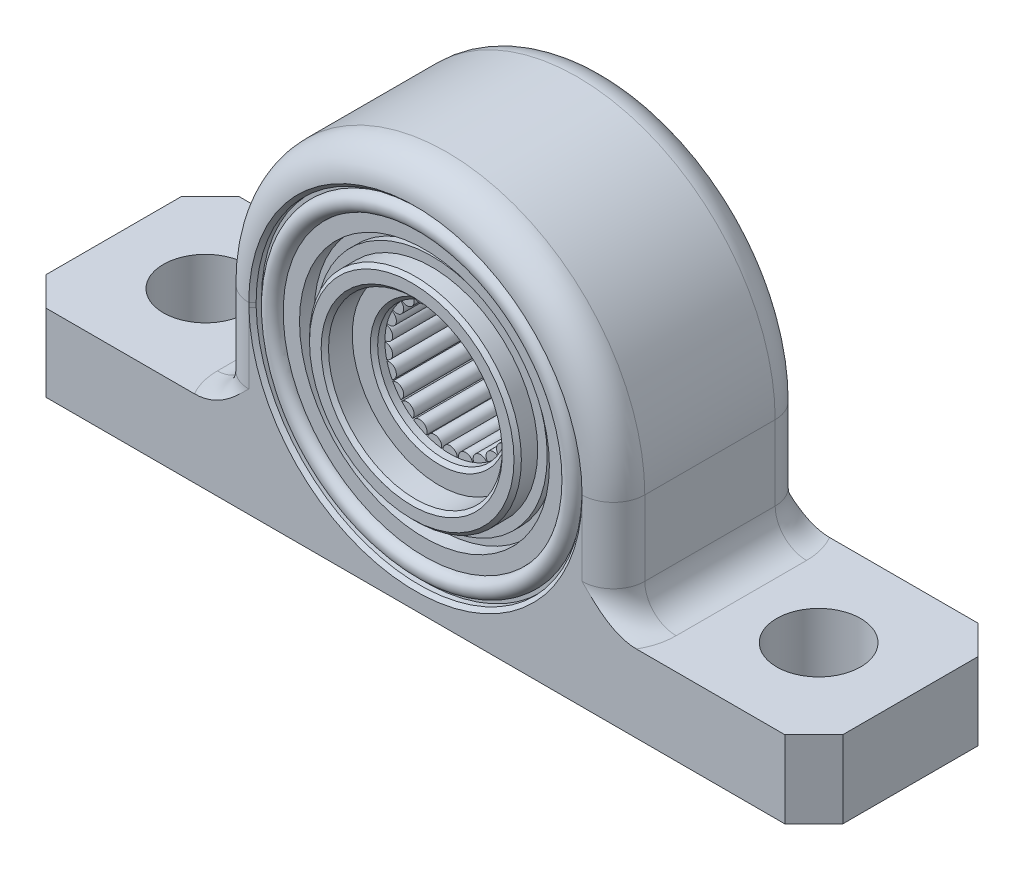
SolidWorks part; units mm, degrees
ref_plane "Front Plane" through (0, 0, 0) normal (0, 0, 1) x (1, 0, 0)
ref_plane "Top Plane" through (0, 0, 0) normal (0, 1, 0) x (1, 0, 0)
ref_plane "Right Plane" through (0, 0, 0) normal (1, 0, 0) x (0, 0, -1)
sketch "Sketch1" plane through (0, 0, 0) normal (0, 0, 1) x (1, 0, 0)
  line L0 (0, 19.75) -> (0, -19.75) construction
  line L1 (-41.25, -19.75) -> (41.25, -19.75) construction
  line L2 (-31.75, -19.75) -> (31.75, -19.75) construction
  line L3 (-41.25, -19.75) -> (-41.25, -11.75)
  line L4 (-41.25, -11.75) -> (-20.5, -11.75)
  line L5 (-20.5, -0.75) -> (-20.5, -11.75)
  line L6 (-23.75, -19.75) -> (-23.75, -11.75) construction
  circle A0 centre (-31.75, -19.75) radius 4.35
  circle A1 centre (31.75, -19.75) radius 4.35
  circle A2 centre (0, -0.75) radius 6
  circle A3 centre (0, -0.75) radius 20.5
  circle A4 centre (-31.75, -19.75) radius 8
  circle A5 centre (0, -0.75) radius 16.875
  circle A6 centre (0, -0.75) radius 9
  circle A7 centre (0, -0.75) radius 6.75 construction
  point P5 (0, -11.75)
  point P6 (0, -0.75)
  point P7 (-31.75, -19.75)
  point P8 (31.75, -19.75)
  point P22 (0, 5.25)
  point P23 (0, 16.125)
  point P25 (0, 13.875)
  point P26 (0, 12.1875)
  point P27 (0, 10.2187)
  point P28 (0, 8.25)
  dimension "D1" = 3.25
  dimension "Mounting Hole" = 8.7
  dimension "ID" = 12
  dimension "D3" = 10.875
  dimension "D4" = 18
  dimension "D9" = 13.5
  dimension "Height" = 39.5
  dimension "Length" = 82.5
  dimension "Lit G" = 8
  dimension "Center Height" = 19
  dimension "Mounting Center" = 63.5
  dimension "D2" = 14.5
  dimension "D5" = 7.875
  dimension "D6" = 2.25
  dimension "D7" = 1.9687
  dimension "D8" = 1.9687
sketch "Sketch3" plane through (0, 0, 0) normal (0, 1, 0) x (1, 0, 0)
  line L0 (0, 10) -> (0, -10) construction
  point P2 (0, -10)
  point P4 (0, 9.5)
  dimension "Width" = 20
  dimension "CAD C" = 20
  dimension "D" = 19.5
sketch "Sketch6" plane through (0, 0, 0) normal (1, 0, 0) x (0, 0, -1)
  line L0 (-9.0655, 15.744) -> (-9.0655, 16.125)
  line L1 (-10, 16.125) -> (10, 16.125) construction
  line L2 (-10, 16.125) -> (-10, -0.75) construction
  line L3 (-10, -0.75) -> (10, -0.75) construction
  line L4 (10, 16.125) -> (10, -0.75) construction
  line L5 (-9.0655, 13.875) -> (-9.0655, 12.1875)
  line L6 (-7.5415, 12.1875) -> (-9.0655, 12.1875)
  line L7 (-8.3035, 11.2031) -> (-8.3035, 10.2187)
  line L8 (-8.3035, 10.2187) -> (-10.381, 10.2187)
  line L9 (-10.381, 10.2187) -> (-10.381, 8.25)
  line L10 (-8.3035, 11.2031) -> (-7.5415, 11.2031)
  line L11 (-7.5415, 11.2031) -> (-7.5415, 12.1875)
  line L12 (-10.381, 8.25) -> (-7.5415, 8.25)
  line L13 (-7.5415, 8.25) -> (-7.5415, 5.25)
  line L14 (-7.5415, 5.25) -> (7.5415, 5.25)
  line L15 (-9.0655, 16.125) -> (9.0655, 16.125)
  line L16 (0, -0.75) -> (0, 32.5437) construction
  line L17 (0, 19.75) -> (0, -19.75) construction
  line L18 (0, 19.75) -> (0, -21.25) construction
  line L19 (7.5415, 8.25) -> (7.5415, 5.25)
  line L20 (10.381, 8.25) -> (7.5415, 8.25)
  line L21 (7.5415, 11.2031) -> (7.5415, 12.1875)
  line L22 (8.3035, 11.2031) -> (7.5415, 11.2031)
  line L23 (10.381, 10.2187) -> (10.381, 8.25)
  line L24 (8.3035, 10.2187) -> (10.381, 10.2187)
  line L25 (8.3035, 11.2031) -> (8.3035, 10.2187)
  line L26 (7.5415, 12.1875) -> (9.0655, 12.1875)
  line L27 (9.0655, 13.875) -> (9.0655, 12.1875)
  line L28 (9.0655, 15.744) -> (9.0655, 16.125)
  arc A0 (-9.0655, 15.744) -> (-9.0655, 13.875) centre (-9.0655, 14.8095) ccw
  arc A1 (9.0655, 15.744) -> (9.0655, 13.875) centre (9.0655, 14.8095) cw
  point P40 (0, 16.125)
  point P41 (0, 5.25)
  dimension "D1" = 0.381
  dimension "D2" = 0.381
  dimension "D3" = 1.524
  dimension "D4" = 0.762
  dimension "D5" = 0.762
  dimension "D6" = 15.083
revolve "Revolve1" add sketch "Sketch6" angle 360 about L3
sketch "Sketch7" plane through (0, 0, 0) normal (0, 0, 1) x (1, 0, 0)
  line L0 (0, 19.75) -> (0, -19.75) construction
  line L1 (-0.75, 6) -> (0, -0.75) construction
  line L2 (0, -0.75) -> (0.75, 6) construction
  circle A0 centre (0, 6) radius 0.75
  circle A1 centre (0, -0.75) radius 6.75 construction
  circle A2 centre (0, -0.75) radius 6 construction
  dimension "D1" = 1.5
  dimension "D2" = 12.68
sketch "Sketch8" plane through (0, 0, 7.5415) normal (0, 0, 1) x (1, 0, 0)
  circle A0 centre (0, -0.75) radius 6.75 construction
  circle A1 centre (0, -0.75) radius 6.75
extrude "Cut-Extrude2" cut sketch "Sketch8" against normal through all
sketch "Sketch9" plane through (0, 0, 0) normal (0, 0, 1) x (1, 0, 0)
  circle A0 centre (0, 6) radius 0.75 construction
  circle A1 centre (0, 6) radius 0.75
extrude "Boss-Extrude2" add sketch "Sketch9" along normal mid plane 12.8205
pattern_circular "CirPattern1" count 26 over 360 of "Boss-Extrude2"
chamfer "Chamfer2" distance 0.381 angle 45 6 edges at (9, -0.75, -10.381) (10.9688, -0.75, -10.381) (10.9688, -0.75, 10.381) (9, -0.75, 10.381) (6.75, -0.75, -7.5415) (6.75, -0.75, 7.5415)
sketch "Sketch4" plane through (0, 0, 0) normal (0, 0, 1) x (1, 0, 0)
  line L0 (-41.25, -19.75) -> (-41.25, -11.75) construction
  line L1 (-41.25, -11.75) -> (-20.5, -11.75) construction
  line L2 (-41.25, -19.75) -> (41.25, -19.75) construction
  line L3 (-41.25, -19.75) -> (-41.25, -11.75)
  line L4 (-41.25, -11.75) -> (-20.5, -11.75)
  line L5 (-41.25, -19.75) -> (41.25, -19.75)
  line L6 (-20.5, -0.75) -> (-20.5, -11.75) construction
  line L7 (-20.5, -0.75) -> (-20.5, -11.75)
  line L8 (0, 19.75) -> (0, -19.75) construction
  line L9 (20.5, -0.75) -> (20.5, -11.75)
  line L10 (41.25, -11.75) -> (20.5, -11.75)
  line L11 (41.25, -19.75) -> (41.25, -11.75)
  circle A0 centre (0, -0.75) radius 20.5 construction
  arc A1 (20.5, -0.75) -> (-20.5, -0.75) centre (0, -0.75) ccw
  circle A2 centre (0, -0.75) radius 16.875 construction
  circle A3 centre (0, -0.75) radius 16.875
extrude "Boss-Extrude1" add sketch "Sketch4" along normal up to vertex (10 mm away) and the other way up to vertex (10 mm away) up to point (0, 0, 10) other way up to point (0, 0, -10)
sketch "Sketch5" plane through (0, -11.75, 0) normal (0, 1, 0) x (1, 0, 0)
  circle A0 centre (-31.75, 0) radius 4.35
  circle A1 centre (31.75, 0) radius 4.35
  dimension "D1" = 8.7
extrude "Cut-Extrude1" cut sketch "Sketch5" against normal through all
chamfer "Chamfer1" distance 3 angle 45 4 edges at (41.25, -15.75, -10) (41.25, -15.75, 10) (-41.25, -15.75, 10) (-41.25, -15.75, -10)
fillet "Fillet1" radius 3.25 6 edges at (20.5, -6.25, -10) (0, 19.75, -10) (20.5, -6.25, 10) (0, 19.75, 10) (-20.5, -6.25, -10) (-20.5, -6.25, 10)
fillet "Fillet3" radius 3.25 6 edges at (-19.5481, -11.75, -9.0481) (-19.5481, -11.75, 9.0481) (-20.5, -11.75, 0) (19.5481, -11.75, -9.0481) (20.5, -11.75, 0) (19.5481, -11.75, 9.0481) tangent propagation no
chamfer "Chamfer3" distance 0.381 angle 45 2 edges at (16.875, -0.75, -10) (16.875, -0.75, 10)
equation "\"D1@Sketch5\"=\"Mounting Hole@Sketch1\""
equation "\"D1@Chamfer1\"=\"Width@Sketch3\"*.15"
equation "\"D1@Fillet1\"=\"D1@Sketch1\""
equation "\"D1@Fillet3\"=\"D1@Fillet1\""
equation "\"D3@Sketch1\"=\"D2@Sketch1\"*.750"
equation "\"D4@Sketch1\"=\"ID@Sketch1\"*1.5"
equation "\"D6@Sketch1\"=\"D5@Sketch1\"/3.5"
equation "\"D7@Sketch1\"=\"D5@Sketch1\"/4"
equation "\"D8@Sketch1\"=\"D5@Sketch1\"/4"
equation "\"D9@Sketch1\"=\"ID@Sketch1\"*1.125"
equation "\"D1@CirPattern1\"=(360/\"D2@Sketch7\")-2"
equation "\"D1@Boss-Extrude2\"=\"D6@Sketch6\"*.85"
